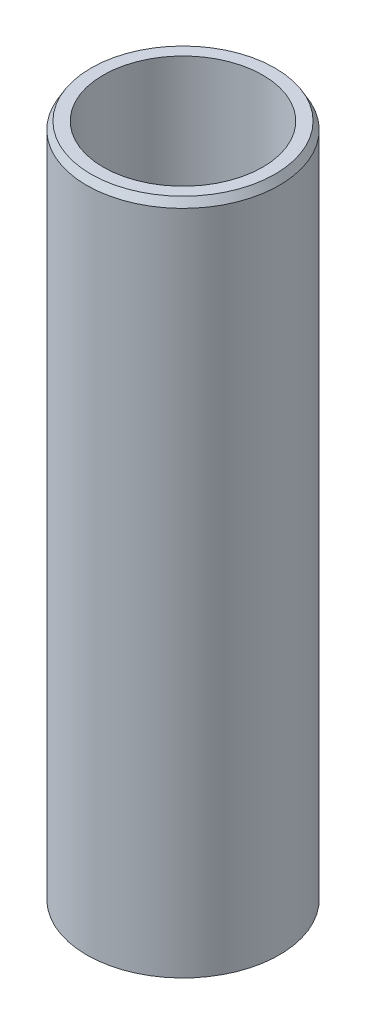
SolidWorks part; units mm, degrees
ref_plane "Front Plane" through (0, 0, 0) normal (0, 0, 1) x (1, 0, 0)
ref_plane "Top Plane" through (0, 0, 0) normal (0, 1, 0) x (1, 0, 0)
ref_plane "Right Plane" through (0, 0, 0) normal (1, 0, 0) x (0, 0, -1)
sketch "Sketch1" plane through (0, 0, 0) normal (0, 1, 0) x (1, 0, 0)
  circle A0 centre (0, 0) radius 57.5
  dimension "SHAFT_OD" = 115
extrude "Boss-Extrude1" add sketch "Sketch1" along normal blind 404.9541
sketch "Sketch2" plane through (0, 0, 0) normal (0, 1, 0) x (1, 0, 0)
  circle A0 centre (0, 0) radius 47.6275
  dimension "BORE_D" = 95.255
extrude "Cut-Extrude1" cut sketch "Sketch2" along normal through all
chamfer "Chamfer1" distance 4.4753 angle 30 2 edges at (0, 404.9541, 57.5) (0, 0, 57.5) first distance on face at (0, 404.9541, 57.5) first distance on face at (0, 0, 47.6275)
